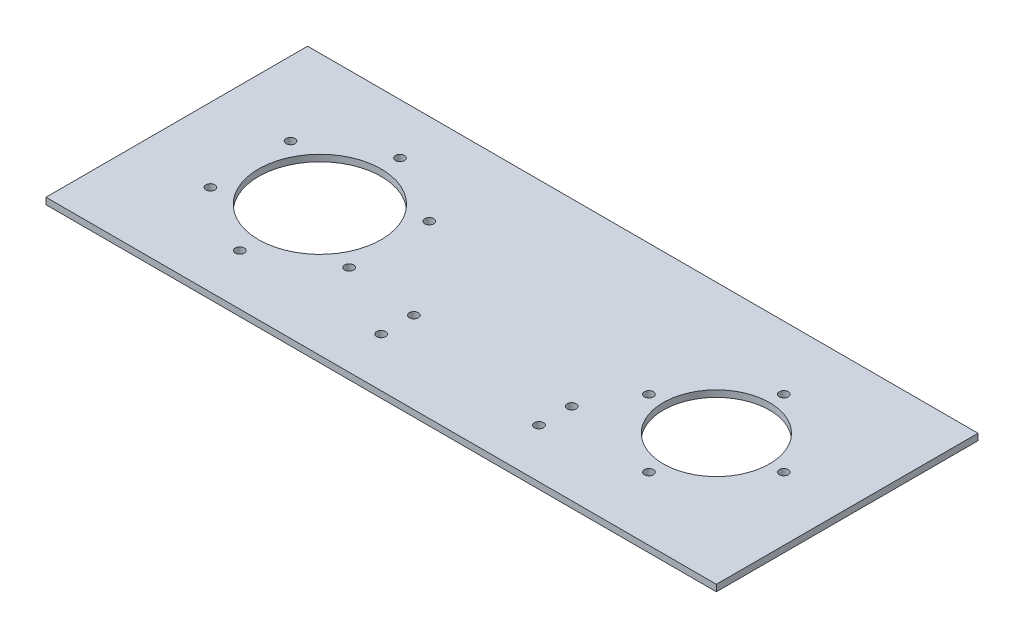
SolidWorks part; units mm, degrees
ref_plane "Front Plane" through (0, 0, 0) normal (0, 0, 1) x (1, 0, 0)
ref_plane "Top Plane" through (0, 0, 0) normal (0, 1, 0) x (1, 0, 0)
ref_plane "Right Plane" through (0, 0, 0) normal (1, 0, 0) x (0, 0, -1)
sketch "Sketch1" plane through (0, 0, 0) normal (0, 1, 0) x (1, 0, 0)
  line L1 (-175, -160) -> (645, -160)
  line L2 (-175, -160) -> (-175, 160)
  line L3 (-175, 160) -> (645, 160)
  line L4 (645, -160) -> (645, 160)
  circle A0 centre (0, 0) radius 75
  circle A1 centre (0, 0) radius 98 construction
  circle A2 centre (0, -98) radius 5.5
  circle A3 centre (-84.8705, -49) radius 5.5
  circle A4 centre (-84.8705, 49) radius 5.5
  circle A5 centre (0, 98) radius 5.5
  circle A6 centre (84.8705, 49) radius 5.5
  circle A7 centre (84.8705, -49) radius 5.5
  circle A8 centre (485, 0) radius 65
  circle A9 centre (485, 0) radius 82.5 construction
  circle A10 centre (567.5, 0) radius 5.5
  circle A14 centre (485, -82.5) radius 5.5
  circle A15 centre (402.5, 0) radius 5.5
  circle A16 centre (485, 82.5) radius 5.5
  point P4 (-175, 0)
  point P23 (0, 0)
  point P36 (250, 0)
  point P37 (485, 0)
  dimension "D2" = 150
  dimension "D3" = 196
  dimension "D4" = 11
  dimension "D8" = 130
  dimension "D9" = 165
  dimension "D10" = 11
  dimension "D1" = 320
  dimension "D6" = 175
  dimension "D7" = 485
  dimension "D12" = 820
  dimension "D5" = 6
  dimension "D11" = 4
extrude "Boss-Extrude1" add sketch "Sketch1" along normal blind 8 contours L1 L4 L3 L2 A10 A8 A7 A6 A5 A4 A3 A2 A0 region at (238.7893, 0, 0)
sketch "Sketch2" plane through (0, 0, 0) normal (0, 1, 0) x (1, 0, 0)
  line L0 (235, 160) -> (235, -160) construction
  line L1 (-175, 160) -> (645, 160) construction
  line L2 (-175, -160) -> (645, -160) construction
  line L3 (175, -60) -> (368, -60) construction
  line L4 (368, -60) -> (368, -100) construction
  line L5 (368, -100) -> (175, -100) construction
  line L6 (175, -100) -> (175, -60) construction
  circle A0 centre (175, -60) radius 5.5
  circle A1 centre (175, -100) radius 5.5
  circle A2 centre (368, -100) radius 5.5
  circle A3 centre (368, -60) radius 5.5
  dimension "D5" = 11
  dimension "D1" = 193
  dimension "D2" = 40
  dimension "D3" = 60
  dimension "D4" = 60
extrude "Cut-Extrude2" cut sketch "Sketch2" along normal blind 10
equation "\"d_ext_rouleau\"= 90"
equation "\"epaisseur_rouleau\"=80"
equation "\"alesage-rouleau\"= 52"
equation "\"jeu_dent_rouleau\"= 2"
equation "\"profondeur_dent_rouleau\"=4"
equation "\"n_dent_roueau\"= 15"
equation "\"d_ext_roulement_rouleau\"= 42"
equation "\"d_int_roulement_rouleau\"= 20"
equation "\"B_roulement_rouleau\"= 12"
equation "\"r_roulement_rouleau\"= 0.6"
equation "\"d_bille_roulement_rouleau\"= 8"
equation "\"F_anneau_alesage_rouleau\"=1.85"
equation "\"G_anneau_alesage_rouleau\"=47.5"
equation "\"K_anneau_alesage_rouleau\"=3.75"
equation "\"d_vis_flasque_rouleau\"=5"
equation "\"l-x_vis_flasque_rouleau\"=4"
equation "\"g_anneau_arbre_rouleau\"=19"
equation "\"f_anneau_arbre_rouleau\"=1.3"
equation "\"k_anneau_arbre_rouleau\"=1.5"
equation "\"entrax_vis_rouleau\"=65"
equation "\"d_granulat\"= 8"
equation "\"h_matrice\"= 22"
equation "\"d_matrice\"= 220"
equation "\"zone_vide_matrice\" = 48"
equation "\"d_alesage_matrice\"=20"
equation "\"a_clavette_alesage_matrice\"=6"
equation "\"B_roulement_matrice\"= 12"
equation "\"d_ext_roulement_matrice\"= 42"
equation "\"d_int_roulement_matrice\"= 20"
equation "\"r_roulement_matrice\"= 1"
equation "\"h_epaulement_arbre_matrice\" = 80"
equation "\"j_clavette_arbre_matrice\" = 6"
equation "\"g_anneaux_arbre_matrice\" = 19"
equation "\"f_anneaux_arbre_matrice\" = 1.3"
equation "\"B_roulement_bc_arbre_matrice\"= 10"
equation "\"e_anneaux_arbre_matrice\" = 1.2"
equation "\"h_polie_matrice\" = 40"
equation "\"l_arbre_matrice\" = 300"
equation "\"d_int_ecrou_encouch_matrice\" = 20"
equation "\"d_ext_ecrou_encouch_matrice\" = 32"
equation "\"b_ecrou_encouch_matrice\" = 6"
equation "\"s_ecrou_encouch_matrice\" = 4"
equation "\"G_ecrou_encouch_matrice\" = 1"
equation "\"E_ecrou_encouch_matrice\" = 4"
equation "\"d_int_roulement_conique_matrice\"=25"
equation "\"d_ext_roulement_conique_matrice\"=52"
equation "\"b_roulement_conique_matrice\"=16.25"
equation "\"d_int_roulement_bc_matrice\"=20"
equation "\"d_ext_roulement_bc_matrice\"=42"
equation "\"b_roulement_bc_matrice\" = 12"
equation "\"d_tube_sup_carter\"=244.5"
equation "\"e_tube_sup_carter\"=12"
equation "\"d_tube_inf_catrer\"= 168.3"
equation "\"e_tube_inf_carter\"= 6"
equation "\"d_tube_inf_carter_cache\" = 244.5"
equation "\"e_tube_inf_carter_cache\" = 8"
equation "\"d_tube_sup_carter_cache\" = 133"
equation "\"e_tube_sup_carter_cache\" = 4"
equation "\"h_tube_trimee\" = 40"
equation "\"e_tole\" = 8"
equation "\"entraxe_vis_carter\" = 196"
equation "\"D3@Sketch1\"=\"entraxe_vis_carter\""
equation "\"d_vis_H_carter\"=10"
equation "\"entraxe_courroie\"= 485"
equation "\"D7@Sketch1\"=\"entraxe_courroie\""
equation "\"D10@Sketch1\"=11"
equation "\"d_int_polie_matrice\" = 16"
equation "\"L_base\" = 820"
equation "\"larg_base\" = 320"
equation "\"D1@Sketch1\"=\"larg_base\""
equation "\"D12@Sketch1\"=\"L_base\""
